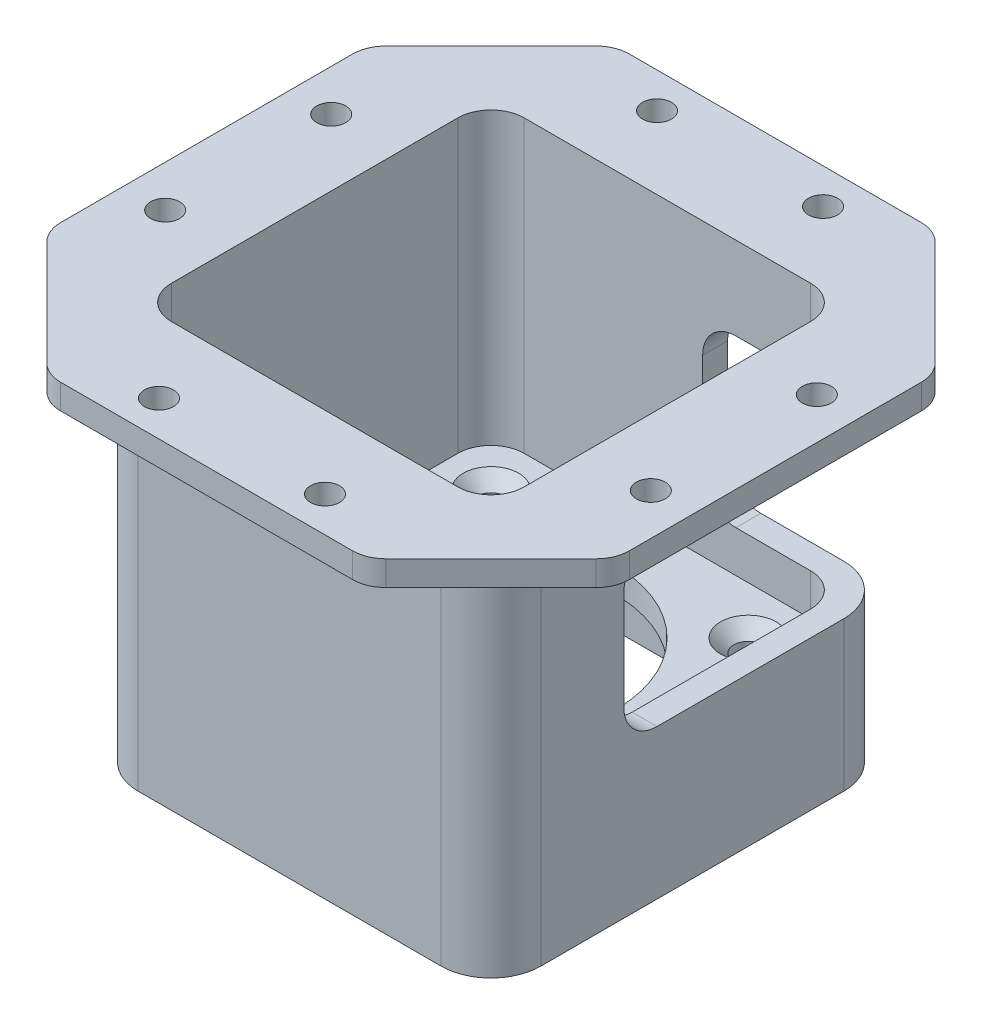
SolidWorks part; units mm, degrees
ref_plane "Front Plane" through (0, 0, 0) normal (0, 0, 1) x (1, 0, 0)
ref_plane "Top Plane" through (0, 0, 0) normal (0, 1, 0) x (1, 0, 0)
ref_plane "Right Plane" through (0, 0, 0) normal (1, 0, 0) x (0, 0, -1)
sketch "Sketch2" plane through (0, 0, 0) normal (0, 1, 0) x (1, 0, 0)
  line L0 (-24.25, 24.25) -> (24.25, 24.25)
  line L1 (-21.25, 21.25) -> (21.25, 21.25) construction
  line L2 (-21.25, 21.25) -> (-21.25, -21.25) construction
  line L3 (-21.25, -21.25) -> (21.25, -21.25) construction
  line L4 (21.25, 21.25) -> (21.25, -21.25) construction
  line L5 (-21.25, 21.25) -> (21.25, -21.25) construction
  line L6 (-21.25, -21.25) -> (21.25, 21.25) construction
  line L7 (24.25, 24.25) -> (24.25, -24.25)
  line L8 (-24.25, -24.25) -> (24.25, -24.25)
  line L9 (-24.25, 24.25) -> (-24.25, -24.25)
  line L10 (-15.5, 15.5) -> (15.5, 15.5) construction
  line L11 (-15.5, 15.5) -> (-15.5, -15.5) construction
  line L12 (-15.5, -15.5) -> (15.5, -15.5) construction
  line L13 (15.5, -15.5) -> (15.5, 15.5) construction
  circle A0 centre (0, 0) radius 15
  circle A1 centre (-15.5, 15.5) radius 1.75
  circle A2 centre (15.5, 15.5) radius 1.75
  circle A3 centre (15.5, -15.5) radius 1.75
  circle A4 centre (-15.5, -15.5) radius 1.75
  point P0 (0, 0)
  dimension "D3" = 30
  dimension "D4" = 3.5
  dimension "D1" = 42.5
  dimension "D2" = 3
  dimension "D5" = 31
extrude "Boss-Extrude1" add sketch "Sketch2" along normal blind 3
sketch "Sketch3" plane through (0, 3, 0) normal (0, 1, 0) x (1, 0, 0)
  line L1 (-21.25, -21.25) -> (21.25, -21.25)
  line L2 (-21.25, -21.25) -> (-21.25, 21.25)
  line L3 (-21.25, 21.25) -> (21.25, 21.25)
  line L4 (21.25, -21.25) -> (21.25, 21.25)
  line L5 (-21.25, -21.25) -> (21.25, 21.25) construction
  line L6 (-21.25, 21.25) -> (21.25, -21.25) construction
  line L7 (-24.25, -24.25) -> (24.25, -24.25)
  line L8 (-24.25, -24.25) -> (-24.25, 24.25)
  line L9 (-24.25, 24.25) -> (24.25, 24.25)
  line L10 (24.25, -24.25) -> (24.25, 24.25)
  line L11 (-24.25, -24.25) -> (24.25, 24.25) construction
  line L12 (-24.25, 24.25) -> (24.25, -24.25) construction
  point P0 (0, 0)
  point P5 (0, 0)
  point P11 (-20.0339, 20.0339)
  dimension "D1" = 42.5
extrude "Boss-Extrude2" add sketch "Sketch3" along normal blind 32
sketch "Sketch4" plane through (0, 35, 0) normal (0, 1, 0) x (1, 0, 0)
  line L1 (-21.25, -21.25) -> (21.25, -21.25)
  line L2 (-21.25, -21.25) -> (-21.25, 21.25)
  line L3 (-21.25, 21.25) -> (21.25, 21.25)
  line L4 (21.25, -21.25) -> (21.25, 21.25)
  line L5 (-21.25, -21.25) -> (21.25, 21.25) construction
  line L6 (-21.25, 21.25) -> (21.25, -21.25) construction
  line L23 (-34.25, 0) -> (34.25, 0) construction
  line L24 (-34.25, 10) -> (34.25, 10) construction
  line L44 (-34.25, -10) -> (34.25, -10) construction
  line L45 (0, -34.25) -> (0, 34.25) construction
  line L46 (34.25, -34.25) -> (34.25, 34.25)
  line L47 (34.25, 34.25) -> (-34.25, 34.25)
  line L48 (-34.25, 34.25) -> (-34.25, -34.25)
  line L49 (-34.25, -34.25) -> (34.25, -34.25)
  line L50 (34.25, -34.25) -> (34.25, 34.25)
  line L51 (34.25, 34.25) -> (-34.25, 34.25)
  line L52 (-34.25, 34.25) -> (-34.25, -34.25)
  line L53 (-34.25, -34.25) -> (34.25, -34.25)
  line L54 (-10, 34.25) -> (-10, -34.25) construction
  line L55 (10, 34.25) -> (10, -34.25) construction
  line L56 (-34.25, 30) -> (34.25, 30) construction
  line L57 (-29.25, 10) -> (-29.25, -10) construction
  line L58 (29.25, 10) -> (29.25, -10) construction
  line L59 (-34.25, -30) -> (34.25, -30) construction
  circle A0 centre (-10, 30) radius 1.75
  circle A1 centre (10, 30) radius 1.75
  circle A2 centre (-29.25, 10) radius 1.75
  circle A3 centre (-29.25, -10) radius 1.75
  circle A4 centre (-10, -30) radius 1.75
  circle A5 centre (10, -30) radius 1.75
  circle A6 centre (29.25, -10) radius 1.75
  circle A7 centre (29.25, 10) radius 1.75
  point P0 (0, 0)
  dimension "D6" = 3.5
  dimension "D7" = 3.5
  dimension "D9" = 3.5
  dimension "D1" = 10
  dimension "D2" = 10
  dimension "D3" = 10
  dimension "D4" = 10
  dimension "D5" = 10
  dimension "D8" = 20
  dimension "D10" = 20
  dimension "D11" = 5
  dimension "D12" = 5
extrude "Boss-Extrude3" add sketch "Sketch4" along normal blind 3
chamfer "Chamfer1" distance 15 angle 45 4 edges at (34.25, 36.5, 34.25) (34.25, 36.5, -34.25) (-34.25, 36.5, -34.25) (-34.25, 36.5, 34.25)
sketch "Sketch5" plane through (0, 0, 0) normal (0, -1, 0) x (1, 0, 0)
  line L1 (-21.25, 21.25) -> (21.25, 21.25)
  line L2 (-21.25, 21.25) -> (-21.25, -21.25)
  line L3 (-21.25, -21.25) -> (21.25, -21.25)
  line L4 (21.25, 21.25) -> (21.25, -21.25)
  line L5 (-21.25, 21.25) -> (21.25, -21.25) construction
  line L6 (-21.25, -21.25) -> (21.25, 21.25) construction
  line L7 (-24.25, -24.25) -> (24.25, -24.25)
  line L8 (-24.25, -24.25) -> (-24.25, 24.25)
  line L9 (-24.25, 24.25) -> (24.25, 24.25)
  line L10 (24.25, -24.25) -> (24.25, 24.25)
  line L11 (-24.25, -24.25) -> (24.25, 24.25) construction
  line L12 (-24.25, 24.25) -> (24.25, -24.25) construction
  line L13 (24.25, -24.25) -> (-24.25, -24.25) construction
  point P0 (0, 0)
  point P5 (0, 0)
  dimension "D1" = 42.5
extrude "Boss-Extrude4" add sketch "Sketch5" along normal blind 10
fillet "Fillet1" radius 6 4 edges at (-24.25, 12.5, 24.25) (-24.25, 12.5, -24.25) (24.25, 12.5, 24.25) (24.25, 12.5, -24.25)
sketch "Sketch7" plane through (24.25, 0, 0) normal (1, 0, 0) x (0, 0, -1)
  line L0 (21.25, 0) -> (-21.25, 0) construction
  line L1 (-8.25, 28) -> (36.75, 28)
  line L2 (-8.25, 28) -> (-8.25, 8)
  line L3 (-8.25, 8) -> (36.75, 8)
  line L4 (36.75, 28) -> (36.75, 8)
  line L5 (-18.25, 35) -> (-18.25, -10) construction
  point P5 (0, 0)
  dimension "D1" = 20
  dimension "D2" = 45
  dimension "D3" = 28
  dimension "D4" = 10
extrude "Cut-Extrude2" cut sketch "Sketch7" against normal blind 20
fillet "Fillet2" radius 4 8 edges at (-19.25, 36.5, 34.25) (-34.25, 36.5, 19.25) (-34.25, 36.5, -19.25) (-19.25, 36.5, -34.25) (19.25, 36.5, -34.25) (34.25, 36.5, -19.25) (19.25, 36.5, 34.25) (34.25, 36.5, 19.25)
chamfer "Chamfer2" distance 1.6 angle 45 4 edges at (-15.5, 3, 17.25) (-15.5, 3, -13.75) (15.5, 3, 17.25) (15.5, 3, -13.75)
fillet "Fillet4" radius 4 5 edges at (-21.25, 20.5, -21.25) (-21.25, 20.5, 21.25) (21.25, 20.5, 21.25) (21.25, 5.5, -21.25) (21.25, 33, -21.25)
fillet "Fillet5" radius 4 4 edges at (22.75, 28, 8.25) (22.75, 8, 8.25) (4.25, 28, -22.75) (4.25, 8, -22.75)
fillet "Fillet6" radius 3 4 edges at (-21.25, -5, -21.25) (-21.25, -5, 21.25) (21.25, -5, -21.25) (21.25, -5, 21.25)
